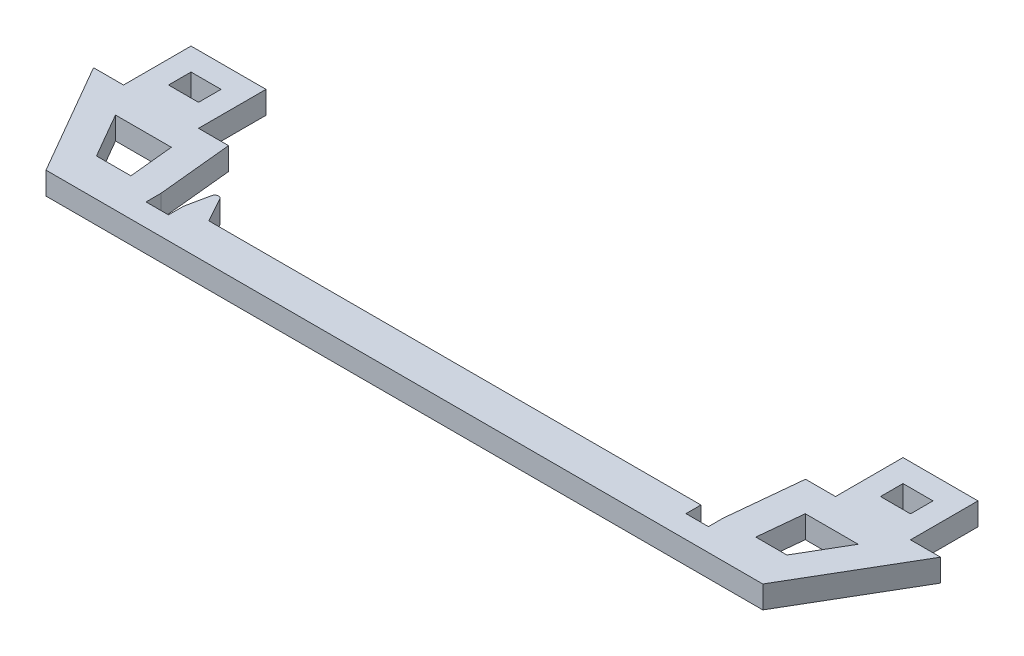
SolidWorks part; units mm, degrees
material "Custom Plastic"
ref_plane "Front Plane" through (0, 0, 0) normal (0, 0, 1) x (1, 0, 0)
ref_plane "Top Plane" through (0, 0, 0) normal (0, 1, 0) x (1, 0, 0)
ref_plane "Right Plane" through (0, 0, 0) normal (1, 0, 0) x (0, 0, -1)
sketch "Sketch1" plane through (0, 0, 0) normal (0, 1, 0) x (1, 0, 0)
  line L0 (-62.4186, -47.1587) -> (-58.4186, -47.1587)
  line L1 (-58.4186, -47.1587) -> (-58.4186, -38.1587)
  line L2 (-58.4186, -38.1587) -> (-48.4186, -38.1587)
  line L3 (-48.4186, -38.1587) -> (-48.4186, -47.1587)
  line L4 (-48.4186, -47.1587) -> (-44.4186, -47.1587)
  line L5 (-44.4186, -47.1587) -> (-43.4188, -57.1562)
  line L7 (31.5814, -57.2088) -> (32.5814, -47.2113)
  line L8 (32.5814, -47.2113) -> (36.5814, -47.2113)
  line L9 (36.5814, -47.2113) -> (36.5814, -38.2113)
  line L10 (36.5814, -38.2113) -> (46.5814, -38.2113)
  line L11 (46.5814, -38.2113) -> (46.5814, -47.2113)
  line L12 (46.5814, -47.2113) -> (50.5814, -47.2113)
  line L13 (50.5814, -47.2113) -> (41.8306, -62.1587)
  line L14 (41.8306, -62.1587) -> (-53.7583, -62.1587)
  line L15 (-53.7583, -62.1587) -> (-62.4186, -47.1587)
  line L16 (36.5478, -51.2113) -> (43.6046, -51.2113)
  line L17 (-55.4186, -41.1587) -> (-51.4186, -41.1587)
  line L18 (-55.4186, -41.1587) -> (-55.4186, -44.1587)
  line L19 (-55.4186, -44.1587) -> (-51.4186, -44.1587)
  line L20 (-51.4186, -41.1587) -> (-51.4186, -44.1587)
  line L21 (39.5814, -41.2113) -> (43.5814, -41.2113)
  line L22 (39.5814, -41.2113) -> (39.5814, -44.2113)
  line L23 (39.5814, -44.2113) -> (43.5814, -44.2113)
  line L24 (43.5814, -41.2113) -> (43.5814, -44.2113)
  line L25 (43.6046, -51.2113) -> (40.0934, -57.2088)
  line L26 (40.0934, -57.2088) -> (35.9479, -57.2088)
  line L27 (35.9479, -57.2088) -> (36.5478, -51.2113)
  line L28 (-55.4904, -51.1587) -> (-48.0385, -51.1587)
  line L29 (-48.0385, -51.1587) -> (-47.4385, -57.1587)
  line L30 (-47.4385, -57.1587) -> (-52.0263, -57.1587)
  line L31 (-52.0263, -57.1587) -> (-55.4904, -51.1587)
  line L32 (28.5814, -57.1587) -> (28.5814, -59.1587)
  line L33 (28.5814, -47.1587) -> (28.5814, -62.1587) construction
  line L34 (28.5814, -59.1587) -> (31.5814, -59.1587)
  line L35 (31.5814, -59.1587) -> (31.5814, -57.2088)
  line L36 (31.5814, -62.1587) -> (31.5814, -47.1587) construction
  line L38 (-43.4188, -57.1562) -> (-43.4188, -59.1587)
  line L39 (-43.4188, -59.1587) -> (-40.4188, -59.1587)
  line L40 (-40.4188, -59.1587) -> (-40.4188, -57.1587)
  line L41 (-37.0377, -57.1587) -> (28.5814, -57.1587)
  line L42 (-37.0377, -57.1587) -> (-38.8414, -53.9008)
  line L44 (-39.7683, -54.0409) -> (-40.4188, -57.1587)
  arc A0 (-39.7683, -54.0409) -> (-38.8414, -53.9008) centre (-39.2789, -54.143) cw
  point P42 (0, 0)
  dimension "D6" = 0.5
  dimension "D1" = 15
  dimension "D2" = 4
  dimension "D3" = 9
  dimension "D4" = 3
  dimension "D5" = 3
  dimension "D7" = 120
  dimension "D8" = 10
  dimension "D9" = 85
  dimension "D10" = 3
  dimension "D11" = 3
  dimension "D12" = 3
  dimension "D13" = 3
  dimension "D14" = 3
  dimension "D15" = 3
  dimension "D17" = 4
  dimension "D18" = 4
  dimension "D19" = 4
  dimension "D20" = 4
  dimension "D21" = 4
  dimension "D23" = 2
  dimension "D24" = 3
extrude "Boss-Extrude1" add sketch "Sketch1" along normal blind 3
